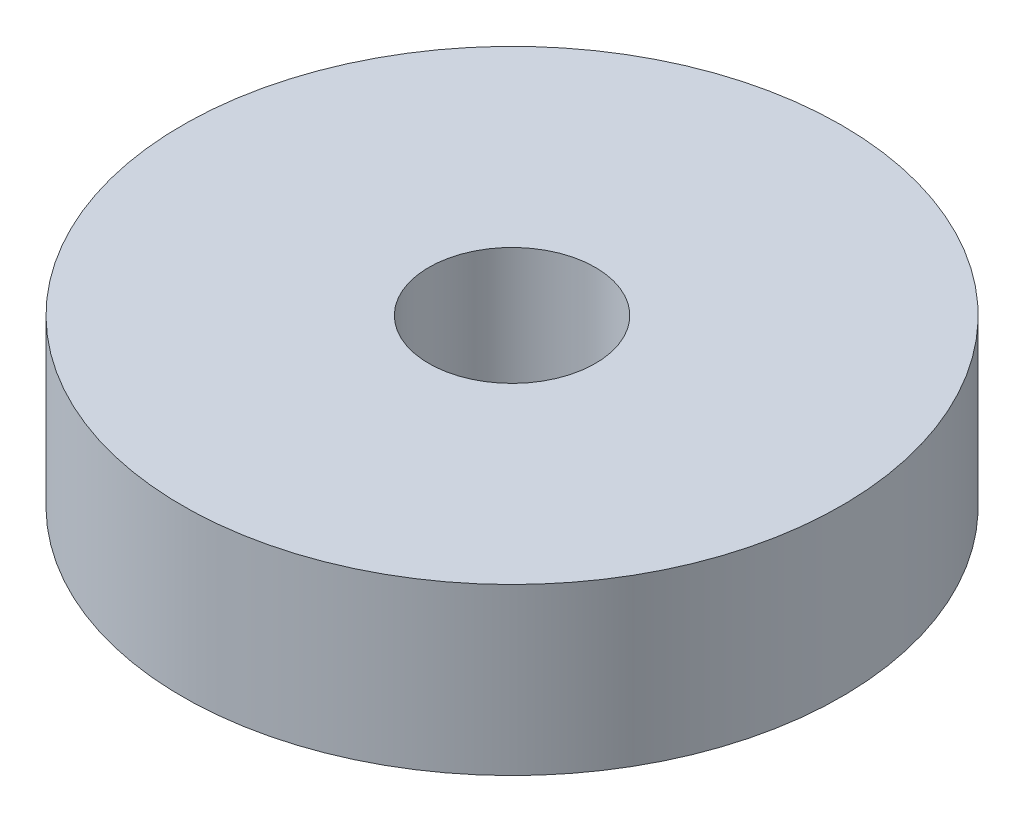
SolidWorks part; units mm, degrees
ref_plane "Front Plane" through (0, 0, 0) normal (0, 0, 1) x (1, 0, 0)
ref_plane "Top Plane" through (0, 0, 0) normal (0, 1, 0) x (1, 0, 0)
ref_plane "Right Plane" through (0, 0, 0) normal (1, 0, 0) x (0, 0, -1)
ref_plane "Shaft Plane" through (0, 0, 24) normal (0, 0, 1) x (1, 0, 0)
sketch "Gear Sketch" plane through (0, 0, 24) normal (0, 0, 1) x (1, 0, 0)
  line L0 (0, -100) -> (0, 200) construction
  line L1 (3.02, 58.5) -> (11.95, 58.5)
  line L2 (11.95, 58.5) -> (11.95, 64.5)
  line L3 (11.95, 64.5) -> (3.02, 64.5)
  line L4 (3.02, 64.5) -> (3.02, 58.5)
revolve "Gear" add sketch "Gear Sketch" angle 360 about L0
ref_axis "Engine Axis" through (13.145, 0, 0) along (-1, 0, 0)
